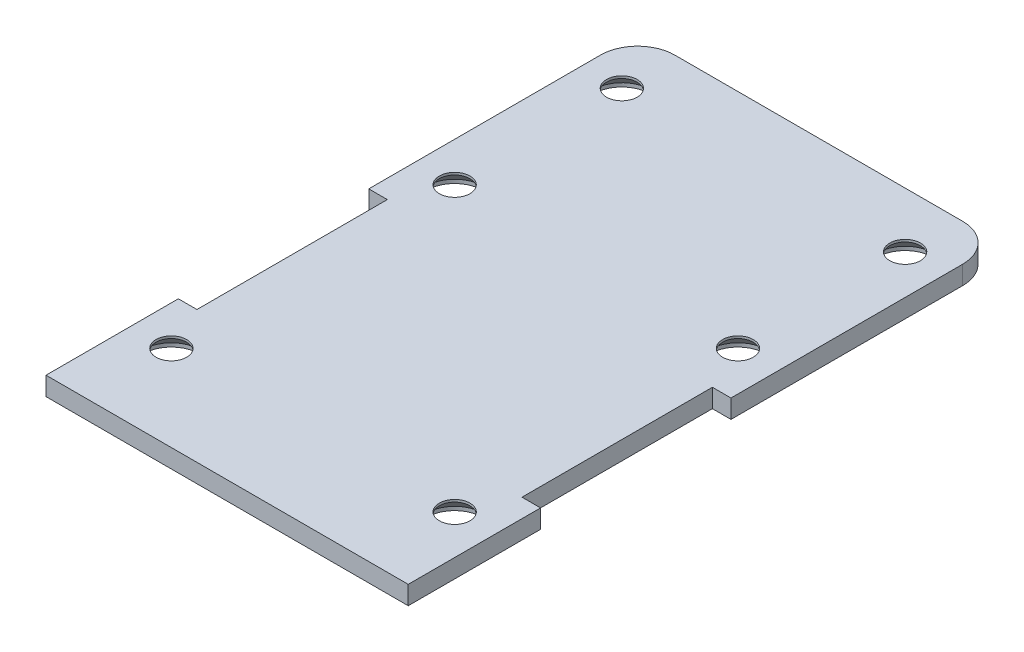
SolidWorks part; units mm, degrees
ref_plane "Front Plane" through (0, 0, 0) normal (0, 0, 1) x (1, 0, 0)
ref_plane "Top Plane" through (0, 0, 0) normal (0, 1, 0) x (1, 0, 0)
ref_plane "Right Plane" through (0, 0, 0) normal (1, 0, 0) x (0, 0, -1)
sketch "Sketch1" plane through (0, 0, 0) normal (0, 1, 0) x (1, 0, 0)
  line L1 (-18, 31.1) -> (18, 31.1)
  line L2 (-18, 31.1) -> (-18, -31.1)
  line L3 (-18, -31.1) -> (18, -31.1)
  line L4 (18, 31.1) -> (18, -31.1)
  line L5 (-18, 31.1) -> (18, -31.1) construction
  line L6 (-18, -31.1) -> (18, 31.1) construction
  point P0 (0, 0)
  dimension "D1" = 36
  dimension "D2" = 62.2
extrude "Base shape" add sketch "Sketch1" along normal blind 2
sketch "Sketch2" plane through (0, 2, 0) normal (0, 1, 0) x (1, 0, 0)
  line L0 (0, 31.1) -> (0, -31.1) construction
  line L1 (18, 31.1) -> (-18, 31.1) construction
  line L2 (-18, -31.1) -> (18, -31.1) construction
  line L4 (-18, 2.15) -> (-17.5, 2.15)
  line L5 (-18, 2.15) -> (-18, -18.35)
  line L6 (-18, -18.35) -> (-17.5, -18.35)
  line L7 (-17.5, 2.15) -> (-17.5, -18.35)
  line L8 (-17.5, -8.1) -> (-18, -8.1) construction
  line L9 (-15.25, -31.1) -> (-15.25, 31.1) construction
  line L11 (-18, -8.1) -> (18, -8.1) construction
  line L13 (15.25, 7.15) -> (15.25, -8.1) construction
  line L14 (15.25, 7.15) -> (0, 7.15) construction
  line L15 (18, -18.35) -> (17.5, -18.35)
  line L16 (17.5, 2.15) -> (17.5, -18.35)
  line L17 (18, 2.15) -> (17.5, 2.15)
  line L18 (18, 2.15) -> (18, -18.35)
  line L19 (18, -31.1) -> (18, 31.1) construction
  line L20 (-18, -31.1) -> (18, -31.1)
  line L21 (-18, -31.1) -> (-18, 14.9)
  line L22 (-18, 14.9) -> (18, 14.9)
  line L23 (18, -31.1) -> (18, 14.9)
  circle A0 centre (15.25, 7.15) radius 1.65
  circle A1 centre (15.25, -23.35) radius 1.65
  circle A2 centre (-15.25, 7.15) radius 1.65
  circle A3 centre (-15.25, -23.35) radius 1.65
  circle A4 centre (-15.25, 25.15) radius 1.65
  circle A5 centre (15.25, 25.15) radius 1.65
  line M13 (18, -31.1) -> (18, 31.1)
  line M15 (-18, 31.1) -> (-18, -31.1)
  dimension "D4" = 3.3
  dimension "D1" = 20.5
  dimension "D2" = 46
  dimension "D3" = 35
  dimension "D5" = 30.5
  dimension "D6" = 18
extrude "Cutouts" cut sketch "Sketch2" against normal up to next contours A2 | A0 | L17 L16 L15 M13 | L7 L4 L6 M15 | A3 | A1 | A4 | A5 region at (-17.75, 2, 8.1) region at (17.75, 2, 8.1) region at (15.25, 2, -7.15) region at (15.25, 2, 23.35) region at (-15.25, 2, -7.15) region at (-15.25, 2, 23.35)
sketch "Sketch3" plane through (0, 0, 0) normal (0, -1, 0) x (1, 0, 0)
  line L0 (18, -16.625) -> (19.5, -16.625) construction
  line L1 (19.5, 32.6) -> (-19.5, 32.6)
  line L2 (19.5, 32.6) -> (19.5, -32.6)
  line L3 (19.5, -32.6) -> (-19.5, -32.6)
  line L4 (-19.5, 32.6) -> (-19.5, -32.6)
  line L5 (19.5, 32.6) -> (-19.5, -32.6) construction
  line L6 (19.5, -32.6) -> (-19.5, 32.6) construction
  line L7 (0, -31.1) -> (0, -32.6) construction
  line L8 (-19.5, -31.1) -> (19.5, -31.1)
  line L9 (-19.5, -2.15) -> (19.5, -2.15)
  line L10 (-19.5, 18.35) -> (19.5, 18.35)
  line L11 (-19.5, 31.1) -> (19.5, 31.1)
  line L12 (-18, 18.35) -> (-17.5, 18.35)
  line L13 (-18, 31.1) -> (-18, 18.35)
  line L14 (18, 31.1) -> (-18, 31.1)
  line L15 (18, 18.35) -> (18, 31.1)
  line L16 (17.5, 18.35) -> (18, 18.35)
  line L17 (17.5, -2.15) -> (17.5, 18.35)
  line L18 (18, -2.15) -> (17.5, -2.15)
  line L19 (18, -31.1) -> (18, -2.15)
  line L20 (-18, -31.1) -> (18, -31.1)
  line L21 (-18, -2.15) -> (-18, -31.1)
  line L22 (-17.5, -2.15) -> (-18, -2.15)
  line L23 (-17.5, 18.35) -> (-17.5, -2.15)
  line L24 (-18, 18.35) -> (-17.5, 18.35)
  line L25 (-18, 31.1) -> (-18, 18.35)
  line L26 (18, 31.1) -> (-18, 31.1)
  line L27 (18, 18.35) -> (18, 31.1)
  line L28 (17.5, 18.35) -> (18, 18.35)
  line L29 (17.5, -2.15) -> (17.5, 18.35)
  line L30 (18, -2.15) -> (17.5, -2.15)
  line L31 (18, -31.1) -> (18, -2.15)
  line L32 (-18, -31.1) -> (18, -31.1)
  line L33 (-18, -2.15) -> (-18, -31.1)
  line L34 (-17.5, -2.15) -> (-18, -2.15)
  line L35 (-17.5, 18.35) -> (-17.5, -2.15)
  point P2 (0, 0)
  line M15 (18, -31.1) -> (18, -2.15)
  line M16 (18, 31.1) -> (-18, 31.1)
  line M17 (-18, 31.1) -> (-18, 18.35)
  line M35 (-18, -2.15) -> (-18, -31.1)
  line M36 (18, 18.35) -> (18, 31.1)
  dimension "D2" = 1.5
  dimension "D1" = 0
extrude "Extra size" add sketch "Sketch3" against normal up to surface (2 mm away) contours L9 L4 L8 M35 | L9 L8 L2 M15 | L11 L4 L10 M17 | L11 L10 L2 M36 | L4 L11 L2 L1 M16 region at (0, 0, 31.85) region at (18.75, 0, 24.725) region at (-18.75, 0, 24.725) region at (18.75, 0, -16.625) region at (-18.75, 0, -16.625) up to face at (15.25, 2, 25)
sketch "Sketch4" plane through (0, 0, 0) normal (0, 1, 0) x (1, 0, 0)
  circle A0 centre (-15.25, 25.15) radius 3
  circle A1 centre (15.25, 25.15) radius 3
  circle A2 centre (15.25, 7.15) radius 3
  circle A3 centre (-15.25, 7.15) radius 3
  circle A4 centre (-15.25, -23.35) radius 3
  circle A5 centre (15.25, -23.35) radius 3
  dimension "D1" = 6
extrude "Screw head cut" cut sketch "Sketch4" along normal blind 0.4
chamfer "Screw chamfer" distance 1.35 angle 45 6 edges at (-15.25, 0.4, 25) (15.25, 0.4, 25) (15.25, 0.4, -5.5) (15.25, 0.4, -23.5) (-15.25, 0.4, -23.5) (-15.25, 0.4, -5.5)
fillet "Fillet1" radius 4 2 edges at (19.5, 1, -31.1) (-19.5, 1, -31.1)
